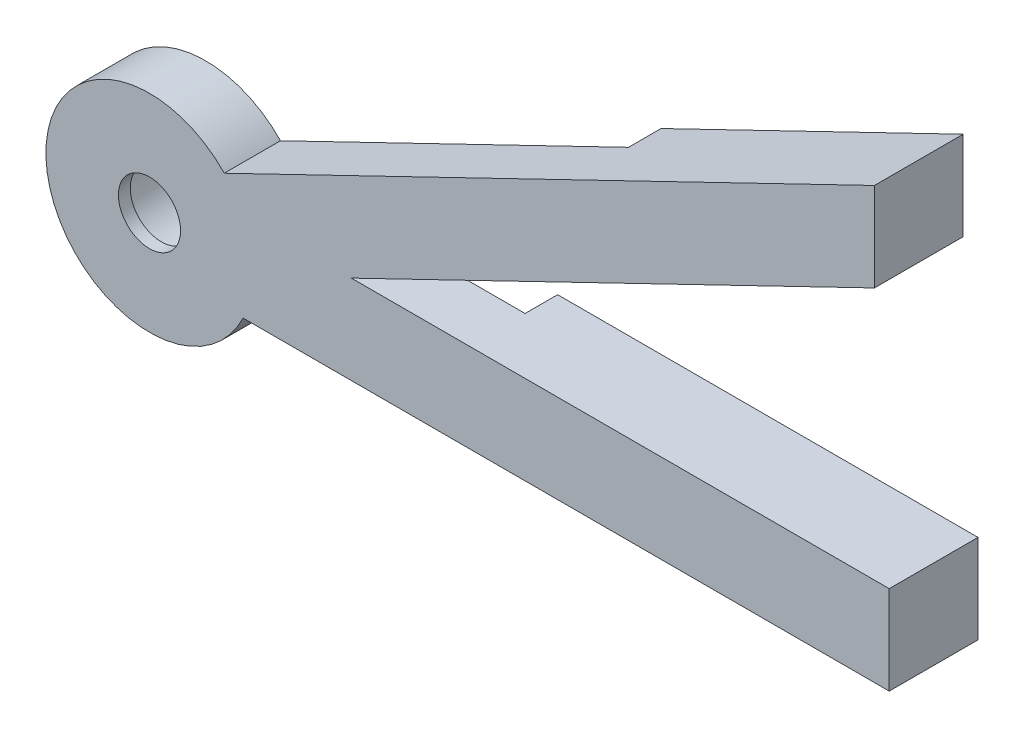
SolidWorks part; units mm, degrees
ref_plane "Front Plane" through (0, 0, 0) normal (0, 0, 1) x (1, 0, 0)
ref_plane "Top Plane" through (0, 0, 0) normal (0, 1, 0) x (1, 0, 0)
ref_plane "Right Plane" through (0, 0, 0) normal (1, 0, 0) x (0, 0, -1)
sketch "Sketch1" plane through (0, 0, 0) normal (0, 0, 1) x (-1, 0, 0)
  line L32 (-15.4758, -28.2324) -> (-15.4758, -34.2324)
  line L33 (27.1997, -5.1324) -> (-16.4758, -5.1324)
  line L34 (-15.4758, -28.2324) -> (19.8777, -11.1324)
  line L35 (-15.4758, -34.2324) -> (28.4707, -12.9761)
  line L36 (-16.4758, -5.1324) -> (-16.4758, -11.1324)
  line L37 (13.5242, -8.1324) -> (11.938, -11.1324)
  line L38 (19.8777, -11.1324) -> (-16.4758, -11.1324)
  line L39 (4.9473, -24.354) -> (9.2098, -16.2923)
  arc A5 (28.4707, -12.9761) -> (27.1997, -5.1324) centre (33.5242, -8.1324) ccw
  arc A6 (13.5242, -8.1324) -> (13.7505, -5.1324) centre (33.5242, -8.1324) cw
  circle A7 centre (33.5242, -8.1324) radius 2.1
  dimension "D1" = 4.2
extrude "Boss-Extrude2" add sketch "Sketch1" against normal blind 6 contours L35 L39 L34 L32 | L37 A6 L33 L36 L38 region at (4.1651, 25.667, 0) region at (1.6503, 8.1028, 0)
extrude "Boss-Extrude3" add sketch "Sketch1<3>" against normal blind 3.8 contours A6 L37 L38 L34 L39 L35 A5 L33 region at (-24.5029, 10.8152, 0)
sketch "Sketch1<3>" plane through (0, 0, 0) normal (0, 0, 1) x (-1, 0, 0) same geometry as "Sketch1"
sketch "Sketch3" plane through (0, 0, -3.8) normal (0, 0, -1) x (-1, 0, 0)
  circle A0 centre (33.5242, 8.1324) radius 3.1
  dimension "D1" = 6.2
extrude "Cut-Extrude2" cut sketch "Sketch3" against normal blind 3
